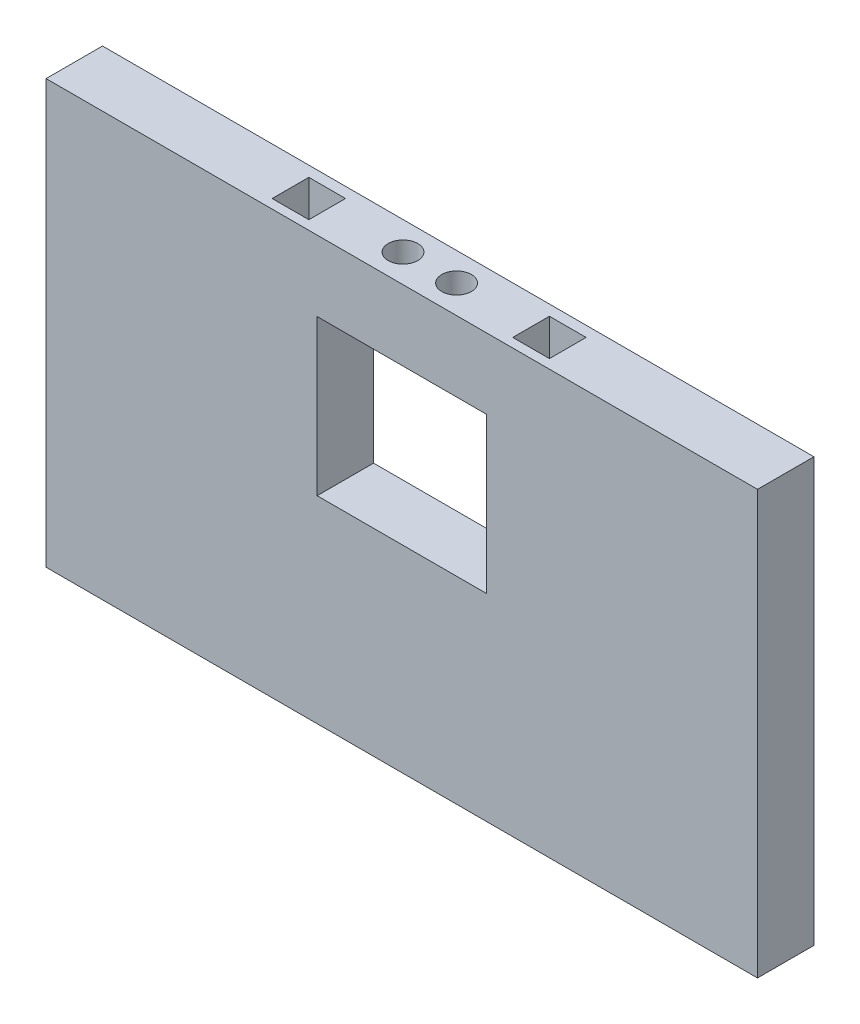
SolidWorks part; units mm, degrees
ref_plane "Front Plane" through (0, 0, 0) normal (0, 0, 1) x (1, 0, 0)
ref_plane "Top Plane" through (0, 0, 0) normal (0, 1, 0) x (1, 0, 0)
ref_plane "Right Plane" through (0, 0, 0) normal (1, 0, 0) x (0, 0, -1)
sketch "Sketch1" plane through (0, 0, 0) normal (0, 0, 1) x (1, 0, 0)
  line L1 (-107.8214, 92.0904) -> (-7.8214, 92.0904)
  line L3 (-107.8214, 44.0904) -> (-7.8214, 44.0904)
  line L5 (-107.8214, 92.0904) -> (-182.8214, 92.0904)
  line L7 (-107.8214, 44.0904) -> (-182.8214, 44.0904)
  line L8 (-182.8214, 92.0904) -> (-182.8214, 44.0904)
  line L9 (-7.8214, 92.0904) -> (117.1786, 92.0904)
  line L11 (-7.8214, 44.0904) -> (117.1786, 44.0904)
  line L12 (117.1786, 92.0904) -> (117.1786, 44.0904)
  dimension "D1" = 48
  dimension "D2" = 100
  dimension "D3" = 75
  dimension "D4" = 125
extrude "Boss-Extrude1" add sketch "Sketch1" along normal blind 20
sketch "Sketch5" plane through (0, 92.0904, 0) normal (0, 1, 0) x (1, 0, 0)
  line L0 (-182.8214, -20) -> (-157.8214, -20) construction
  line L2 (117.1786, -20) -> (-182.8214, -20) construction
  line L3 (-157.8214, -20) -> (-57.8214, -20) construction
  line L4 (-57.8214, -20) -> (-66.3214, -20) construction
  line L5 (-66.3214, -20) -> (-66.3214, -16) construction
  line L6 (-66.3214, -16) -> (-66.3214, -10) construction
  line L7 (-66.3214, -10) -> (-47.3214, -10) construction
  circle A0 centre (-66.3214, -10) radius 5.25
  circle A1 centre (-47.3214, -10) radius 5.25
extrude "Cut-Extrude4" cut sketch "Sketch5" against normal blind 20
sketch "Sketch6" plane through (0, 92.0904, 0) normal (0, 1, 0) x (1, 0, 0)
  line L0 (-182.8214, 0) -> (-105.6914, 0) construction
  line L1 (117.1786, 0) -> (-182.8214, 0) construction
  line L2 (-105.6914, 0) -> (-105.6914, -4) construction
  line L3 (-105.9414, -3.75) -> (-92.9414, -3.75)
  line L8 (-92.9414, -3.75) -> (-92.9414, -16.75)
  line L9 (-105.9414, -16.75) -> (-92.9414, -16.75)
  line L10 (-105.9414, -3.75) -> (-105.9414, -16.75)
extrude "Cut-Extrude5" cut sketch "Sketch6" against normal blind 15.5
sketch "Sketch7" plane through (0, 92.0904, 0) normal (0, 1, 0) x (1, 0, 0)
  line L0 (117.1786, 0) -> (-7.9138, 0) construction
  line L1 (117.1786, 0) -> (-182.8214, 0) construction
  line L2 (-7.9138, 0) -> (-7.9138, -4) construction
  line L3 (-7.6638, -3.75) -> (-20.6638, -3.75)
  line L8 (-20.6638, -3.75) -> (-20.6638, -16.75)
  line L9 (-7.6638, -16.75) -> (-20.6638, -16.75)
  line L10 (-7.6638, -3.75) -> (-7.6638, -16.75)
extrude "Cut-Extrude6" cut sketch "Sketch7" against normal blind 15.5
sketch "Sketch8" plane through (0, 0, 20) normal (0, 0, 1) x (1, 0, 0)
  line L0 (117.1786, 44.0904) -> (117.1786, 92.0904) construction
  line L1 (-182.8214, 44.0904) -> (117.1786, 44.0904)
  line L2 (-182.8214, 44.0904) -> (-182.8214, -57.9096)
  line L3 (-182.8214, -57.9096) -> (117.1786, -57.9096)
  line L4 (117.1786, 44.0904) -> (117.1786, -57.9096)
  dimension "D1" = 150
extrude "Boss-Extrude2" add sketch "Sketch8" against normal up to surface (20 mm away) up to face at (-32.8214, 68.0904, 0)
sketch "Sketch9" plane through (0, 92.0904, 0) normal (0, 1, 0) x (1, 0, 0)
  line L1 (-105.9414, -3.75) -> (-105.9414, -16.75) construction
  line L2 (-7.6638, -3.75) -> (-7.6638, -16.75) construction
  line L4 (117.1786, 0) -> (-182.8214, 0) construction
  line L5 (69.3362, 0) -> (69.3362, -20) construction
  line L6 (117.1786, -20) -> (-182.8214, -20) construction
  line L8 (117.1786, -20) -> (69.3362, -20)
  line L9 (117.1786, -20) -> (117.1786, 0)
  line L10 (117.1786, 0) -> (69.3362, 0)
  line L11 (69.3362, -20) -> (69.3362, 0)
  dimension "D1" = 77
extrude "Cut-Extrude7" cut sketch "Sketch9" against normal up to vertex (150 mm away) up to point (117.1786, -57.9096, 0)
sketch "Sketch11" plane through (0, 0, 20) normal (0, 0, 1) x (1, 0, 0)
  line L0 (69.3362, 92.0904) -> (-182.8214, 92.0904) construction
  line L1 (-56.7426, 92.0904) -> (-56.7426, 62.0904) construction
  line L3 (-26.7426, 62.0904) -> (-26.7426, 12.0904)
  line L4 (-26.7426, 12.0904) -> (-86.7426, 12.0904)
  line L5 (-86.7426, 12.0904) -> (-86.7426, 62.0904)
  line L8 (-26.7426, 62.0904) -> (-26.7426, 64.0904)
  line L9 (-26.7426, 64.0904) -> (-86.7426, 64.0904)
  line L10 (-86.7426, 62.0904) -> (-86.7426, 64.0904)
  point P5 (69.3362, 92.0904)
  point P10 (-56.7426, 62.0904)
  point P12 (-56.7426, 62.0904)
  dimension "D1" = 30
  dimension "D2" = 60
  dimension "D4" = 2
extrude "Cut-Extrude9" cut sketch "Sketch11" against normal blind 40
ref_plane "Plane1" through (-86.7426, 0, 0) normal (1, 0, 0) x (0, 0, -1)
sketch "Sketch14" plane through (-86.7426, 0, 0) normal (1, 0, 0) x (0, 0, -1)
  line L0 (0, 64.0904) -> (-20, 67.0904)
  line L3 (-20, -57.9096) -> (-20, 92.0904) construction
  line L4 (-20, 67.0904) -> (-20, 64.0904)
  line L9 (0, 64.0904) -> (-20, 64.0904)
extrude "Cut-Extrude10" cut sketch "Sketch14" along normal up to surface (60 mm away) up to face at (-26.7426, 38.0904, 10)
